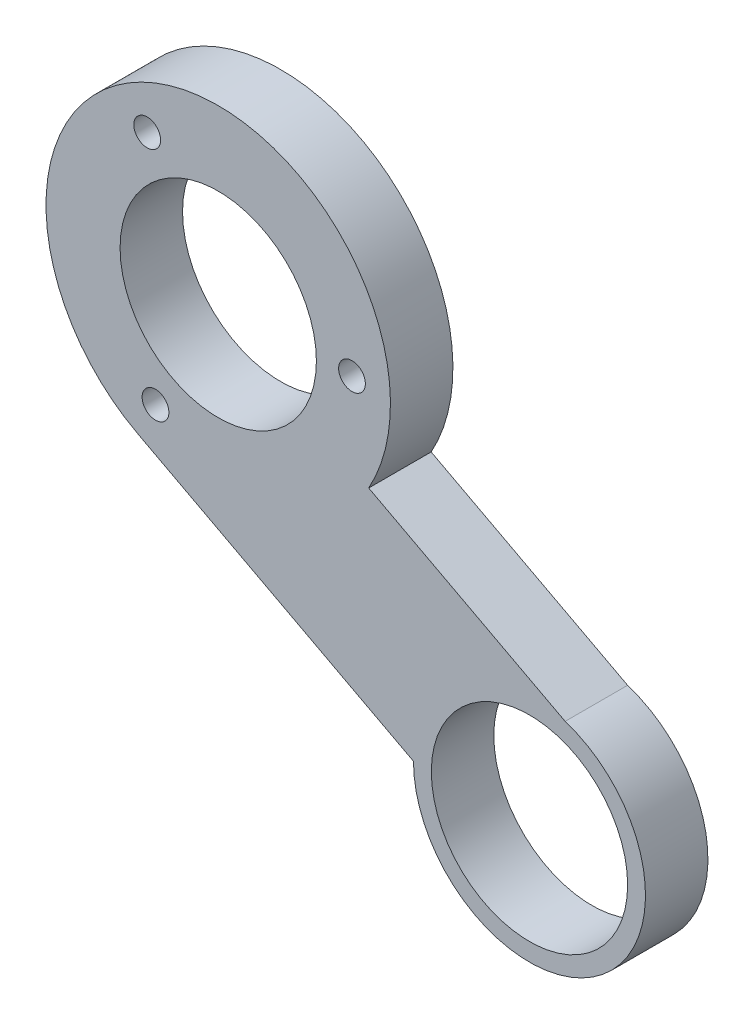
SolidWorks part; units mm, degrees
ref_plane "Front Plane" through (0, 0, 0) normal (0, 0, 1) x (1, 0, 0)
ref_plane "Top Plane" through (0, 0, 0) normal (0, 1, 0) x (1, 0, 0)
ref_plane "Right Plane" through (0, 0, 0) normal (1, 0, 0) x (0, 0, -1)
sketch "Sketch1" plane through (0, 0, 0) normal (0, 0, 1) x (1, 0, 0)
  line L0 (2.7345, -4.0104) -> (24.7494, -15.6495)
  line L1 (-23.1481, -11.6829) -> (7.7527, -28.0199)
  circle A0 centre (-14.1274, 5.3793) radius 19.3
  circle A1 centre (-14.1274, 5.3793) radius 11
  circle A2 centre (-22.0878, 18.0927) radius 1.5
  circle A3 centre (0.863, 5.9165) radius 1.5
  circle A4 centre (-21.1574, -7.8714) radius 1.5
  circle A5 centre (20.7527, -28.0199) radius 11
  circle A6 centre (20.7527, -28.0199) radius 13
  dimension "D1" = 22
  dimension "D2" = 38.6
  dimension "D3" = 22
  dimension "D4" = 26
extrude "Boss-Extrude1" add sketch "Sketch1" along normal up to surface (7 mm away) contours A6 L0 A0 L1 | A0 A4 A3 A2 A1 | L0 A6 A5 region at (3.0456, -15.4746, 0) region at (-8.7973, -12.6014, 0) region at (30.9663, -20.5864, 0)
